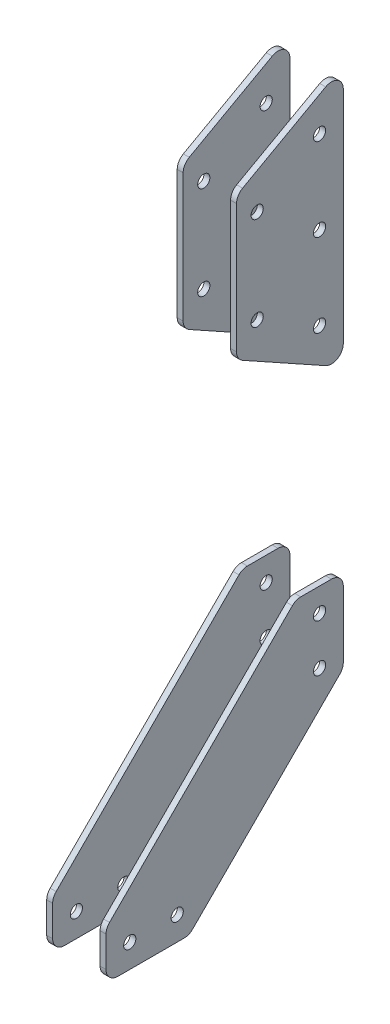
SolidWorks part; units mm, degrees
ref_plane "Front Plane" through (0, 0, 0) normal (0, 0, 1) x (1, 0, 0)
ref_plane "Top Plane" through (0, 0, 0) normal (0, 1, 0) x (1, 0, 0)
ref_plane "Right Plane" through (0, 0, 0) normal (1, 0, 0) x (0, 0, -1)
sketch "Sketch1" plane through (12.7, 0, 0) normal (1, 0, 0) x (0, 0, -1)
  line L0 (-44.45, 317.5) -> (-44.45, 241.3)
  line L1 (-44.45, 241.3) -> (12.7, 209.55)
  line L2 (12.7, 209.55) -> (12.7, 349.25)
  line L3 (12.7, 349.25) -> (-44.45, 317.5)
  line L4 (-44.45, 279.4) -> (12.7, 279.4) construction
  line L5 (0, 279.4) -> (-25.4, 279.4) construction
  line L6 (-44.45, 317.5) -> (-44.45, 241.3) construction
  line L7 (12.7, 406.4) -> (12.7, 12.7) construction
  line L8 (-12.7, 317.5) -> (-44.45, 317.5) construction
  line L9 (-12.7, 114.3) -> (-114.3, 12.7)
  line L10 (-114.3, 12.7) -> (-114.3, -12.7)
  line L11 (-114.3, -12.7) -> (-69.85, -12.7)
  line L12 (-69.85, -12.7) -> (12.7, 69.85)
  line L13 (12.7, 69.85) -> (12.7, 114.3)
  line L14 (12.7, 114.3) -> (-12.7, 114.3)
  line L15 (-355.6, -12.7) -> (152.4, -12.7) construction
  line L16 (-114.3, -12.7) -> (12.7, 114.3) construction
  dimension "D1" = 139.7
  dimension "D2" = 127
  dimension "D3" = 127
  dimension "D4" = 101.6
  dimension "D5" = 82.55
extrude "Boss-Extrude1" add sketch "Sketch1" along normal blind 3.175
sketch "Sketch4" plane through (15.875, 0, 0) normal (1, 0, 0) x (0, 0, -1)
  line L0 (0, 279.4) -> (0, 406.4) construction
  line L1 (0, 279.4) -> (0, 12.7) construction
  line L2 (-355.6, 0) -> (152.4, 0) construction
  line L3 (0, 323.85) -> (0, 234.95) construction
  line L5 (0, 101.6) -> (0, 76.2) construction
  line L7 (-101.6, 0) -> (-76.2, 0) construction
  line L9 (0, 101.6) -> (0, 114.3) construction
  line L10 (12.7, 114.3) -> (-12.7, 114.3) construction
  line L13 (-114.3, 0) -> (-101.6, 0) construction
  line L14 (-114.3, 12.7) -> (-114.3, -12.7) construction
  point P0 (0, 323.85)
  point P4 (0, 234.95)
  point P8 (0, 101.6)
  point P10 (0, 76.2)
  point P12 (-101.6, 0)
  point P16 (-76.2, 0)
  point P19 (0, 279.4)
  point P52 (-33.4, 304.4)
  point P55 (-33.4, 254.4)
  point P59 (-33.4, 254.4)
  dimension "D1" = 88.9
  dimension "D2" = 25.4
  dimension "D3" = 12.7
hole_wizard "1/4 Clearance Hole1" positions "Sketch4" profile "Sketch3" hole size "1/4" standard "ANSI Inch" end condition through all
sketch "Sketch3" plane through (15.875, 323.85, 0) normal (0, 1, 0) x (0, 0, -1)
  line L0 (0, 0) -> (0, 3.175)
  line L1 (0, 3.175) -> (3.2639, 3.175)
  line L2 (3.2639, 3.175) -> (3.2639, 0)
  line L5 (3.2639, 0) -> (0, 0)
  line L11 (0, -6.35) -> (0, 107.95) construction
  dimension "Thru Hole Dia." = 6.5278
  dimension "Thru Hole Depth" = 3.175
fillet "Fillet1" radius 6.35 4 edges at (14.2875, 241.3, 44.45) (14.2875, 209.55, -12.7) (14.2875, 349.25, -12.7) (14.2875, 317.5, 44.45)
fillet "Fillet2" radius 6.35 6 edges at (14.2875, 12.7, 114.3) (14.2875, -12.7, 114.3) (14.2875, -12.7, 69.85) (14.2875, 69.85, -12.7) (14.2875, 114.3, -12.7) (14.2875, 114.3, 12.7)
mirror "Mirror1" about plane through (0, 0, 0) normal (1, 0, 0) of bodies 103 104
